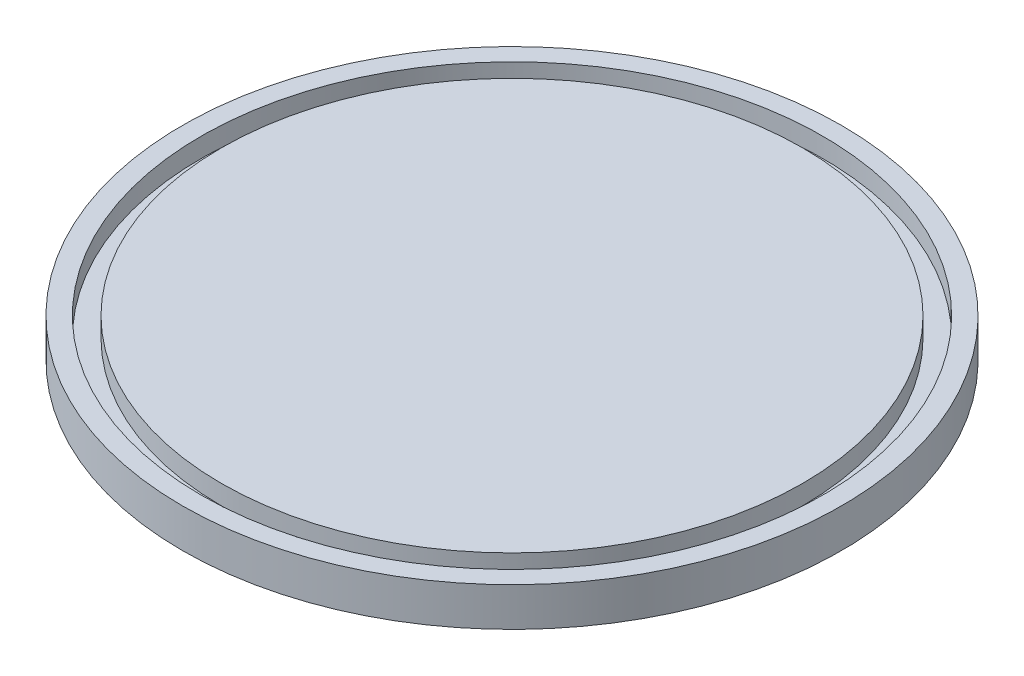
SolidWorks part; units mm, degrees
ref_plane "Front Plane" through (0, 0, 0) normal (0, 0, 1) x (1, 0, 0)
ref_plane "Top Plane" through (0, 0, 0) normal (0, 1, 0) x (1, 0, 0)
ref_plane "Right Plane" through (0, 0, 0) normal (1, 0, 0) x (0, 0, -1)
sketch "Sketch2" plane through (0, 0, 0) normal (0, 0, 1) x (1, 0, 0)
  line L0 (-30, 0) -> (-60, 100) construction
  line L1 (-60, 100) -> (0, 100) construction
  line L2 (0, 100) -> (0, 0) construction
  line L3 (0, 0) -> (-30, 0) construction
  line L4 (-31.4881, -2) -> (-62.6881, 102) construction
  line L5 (-62.6881, 102) -> (2, 102) construction
  line L6 (2, 102) -> (2, -2) construction
  line L9 (-30, 0) -> (-30, -2)
  line L10 (-32.0881, 0) -> (-32.0881, -2)
  line L12 (-30, 0) -> (0, 0)
  line L14 (-30, -2) -> (-32.0881, -2)
  line L16 (-34.0168, 0) -> (-32.0881, 0)
  line L17 (-30, -2) -> (-31.4881, -2) construction
  line L18 (-34.0168, 0) -> (-32.0881, 0)
  line L19 (-34.0168, 0) -> (-34.0168, -4)
  line L20 (-34.0168, -4) -> (0, -4)
  line L21 (0, 0) -> (0, -4)
  line L22 (2, -2) -> (-31.4881, -2) construction
  line L23 (-30, 0) -> (0, 0)
  dimension "D1" = 100
  dimension "D2" = 60
  dimension "D3" = 30
  dimension "D5" = 4
  dimension "D4" = 2
revolve "Revolve1" add sketch "Sketch2" angle 360 about L2 region at (-16.564, -2.0317, 0)
